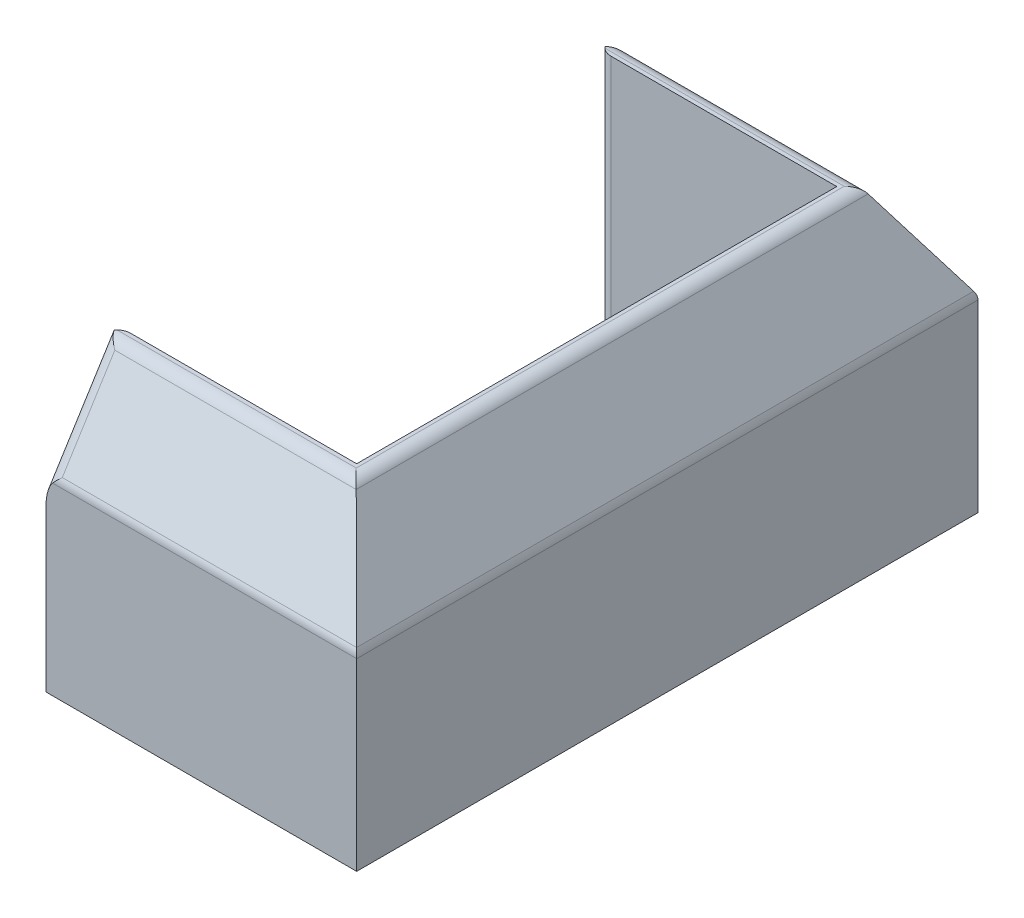
SolidWorks part; units mm, degrees
ref_plane "Front" through (0, 0, 0) normal (0, 0, 1) x (1, 0, 0)
ref_plane "Top" through (0, 0, 0) normal (0, 1, 0) x (1, 0, 0)
ref_plane "Right" through (0, 0, 0) normal (1, 0, 0) x (0, 0, -1)
sketch "Sketch1" plane through (0, 0, 0) normal (0, 1, 0) x (1, 0, 0)
  line L0 (0, 0) -> (0, 16.764)
  line L1 (0, -55) -> (0, 55) construction
  line L2 (0, 16.764) -> (-3.81, 16.764)
  line L3 (-3.81, 16.764) -> (-3.81, 3.81)
  line L4 (-3.81, 3.81) -> (-16.764, 3.81)
  line L5 (-16.764, 3.81) -> (-16.764, 0)
  line L6 (-55, 0) -> (55, 0) construction
  line L7 (-16.764, 0) -> (0, 0)
  dimension "D1" = 16.764
  dimension "D2" = 16.764
  dimension "D3" = 3.81
  dimension "D4" = 3.81
extrude "Boss-Extrude1" add sketch "Sketch1" along normal blind 10.16
sketch "Sketch2" plane through (0, 0, 0) normal (0, 1, 0) x (1, 0, 0)
  line L1 (0, 0) -> (-11.43, 0)
  line L2 (0, 0) -> (0, 11.43)
  line L3 (0, 11.43) -> (-11.43, 11.43)
  line L4 (-11.43, 0) -> (-11.43, 11.43)
  circle A0 centre (-7.874, 7.874) radius 2
  dimension "D2" = 4
  dimension "D1" = 11.43
  dimension "D3" = 3.556
  dimension "D4" = 3.556
extrude "Boss-Extrude2" add sketch "Sketch2" along normal blind 2.54
ref_plane "Plane1" through (0, 15.24, 0) normal (0, 1, 0) x (1, 0, 0)
sketch "Sketch3" plane through (0, 15.24, 0) normal (0, 1, 0) x (1, 0, 0)
  line L0 (-3.2004, 3.175) -> (-3.2004, 16.764)
  line L1 (0, 16.764) -> (-3.81, 16.764) construction
  line L2 (-3.2004, 16.764) -> (-3.81, 16.764)
  line L3 (-3.81, 16.764) -> (-3.81, 3.81)
  line L4 (-3.81, 3.81) -> (-16.764, 3.81)
  line L10 (-3.2004, 3.175) -> (-16.764, 3.175)
  line L11 (-16.764, 3.81) -> (-16.764, 0) construction
  line L12 (-16.764, 3.175) -> (-16.764, 3.81)
  line L13 (-5.588, 0) -> (5.588, 0) construction
  line L14 (0, -5.588) -> (0, 5.588) construction
  dimension "D1" = 3.175
  dimension "D2" = 3.2004
loft "Loft3" add profiles "Sketch3" section face at (-6.858, 10.16, -6.858) section "Sketch3"
mirror "Mirror4" about plane through (0, 10.16, -16.764) normal (0, 0, 1) of bodies 104
fillet "Fillet2" radius 0.762 15 edges at (-11.43, 1.27, -11.43) (-8.382, 10.16, 0) (-8.382, 10.16, -33.528) (-16.764, 7.62, -29.718) (-16.764, 15.24, -30.0355) (-11.43, 1.27, -22.098) (-16.764, 12.7, -31.9405) (-9.9822, 15.24, -30.353) (0, 10.16, -16.764)
